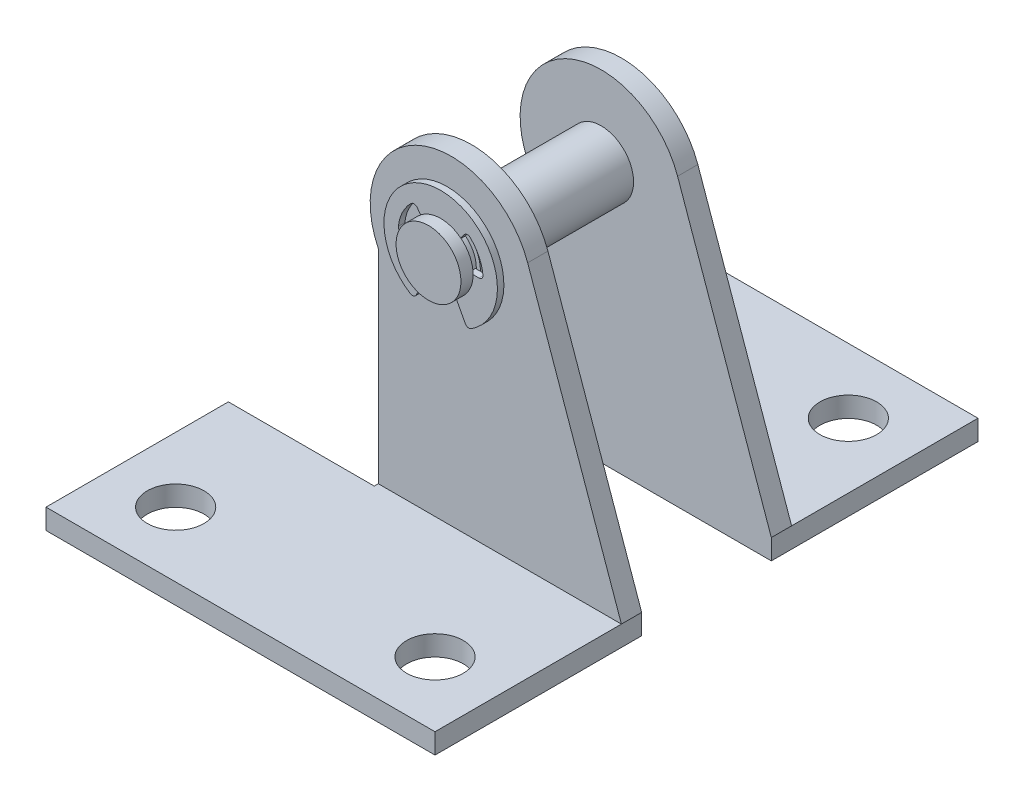
SolidWorks part; units mm, degrees
ref_plane "前视基准面" through (0, 0, 0) normal (0, 0, 1) x (1, 0, 0)
ref_plane "上视基准面" through (0, 0, 0) normal (0, 1, 0) x (1, 0, 0)
ref_plane "右视基准面" through (0, 0, 0) normal (1, 0, 0) x (0, 0, -1)
sketch "草图1" plane through (0, 0, 0) normal (1, 0, 0) x (0, 0, -1)
  line L0 (-13.3, 0) -> (-13.3, 4)
  line L1 (-13.3, 4) -> (-11.8, 4)
  line L2 (-11.8, 4) -> (-11.8, 3.5)
  line L3 (-11.8, 3.5) -> (-10.9, 3.5)
  line L4 (-10.9, 3.5) -> (-10.9, 4)
  line L5 (-10.9, 4) -> (10.9, 4)
  line L6 (10.9, 4) -> (10.9, 3.5)
  line L7 (10.9, 3.5) -> (11.8, 3.5)
  line L8 (11.8, 3.5) -> (11.8, 4)
  line L9 (11.8, 4) -> (13.3, 4)
  line L10 (13.3, 4) -> (13.3, 0)
  line L11 (13.3, 0) -> (-13.3, 0)
  line L12 (13.3, 0) -> (-13.3, 0) construction
revolve "旋转1" add sketch "草图1" angle 360 about L12 reverse direction yes
sketch "草图2" plane through (0, 0, 0) normal (0, 0, 1) x (1, 0, 0)
  line L0 (-9, -4.3589) -> (-9, -32)
  line L1 (-9, -32) -> (21, -32)
  line L2 (21, -32) -> (21, -29.5)
  line L3 (21, -29.5) -> (9.4314, 3.324)
  arc A0 (9.4314, 3.324) -> (-9, -4.3589) centre (0, 0) ccw
extrude "凸台-拉伸1" add sketch "草图2" against normal blind 10.5 and the other way blind 10.5
sketch "草图3" plane through (0, 0, 0) normal (1, 0, 0) x (0, 0, -1)
  line L0 (-8, 56) -> (-8, 4)
  line L1 (-8, 4) -> (8, 4)
  line L2 (8, 4) -> (8, 56)
  line L3 (8, 56) -> (-8, 56)
  line L4 (10, 0) -> (-10, 0) construction
revolve "切除-旋转1" cut sketch "草图3" angle 360 about L4 reverse direction yes
ref_plane "基准面4" through (0, -32, 0) normal (0, 1, 0) x (1, 0, 0)
sketch "草图4" plane through (0, -32, 0) normal (0, 1, 0) x (1, 0, 0)
  line L0 (-27, 33.5) -> (-27, -33.5)
  line L1 (-27, -33.5) -> (21, -33.5)
  line L2 (21, -33.5) -> (21, -8)
  line L3 (21, -8) -> (-9, -8)
  line L4 (-9, -8) -> (-9, 8)
  line L5 (-9, 8) -> (21, 8)
  line L6 (21, 8) -> (21, 33.5)
  line L7 (21, 33.5) -> (-27, 33.5)
  circle A0 centre (13, 25.5) radius 3.5
  circle A1 centre (13, -25.5) radius 3.5
  circle A2 centre (-19, 25.5) radius 3.5
  circle A3 centre (-19, -25.5) radius 3.5
extrude "凸台-拉伸2" add sketch "草图4" along normal blind 2.5
ref_plane "基准面5" through (-9, 0, 0) normal (1, 0, 0) x (0, 0, -1)
sketch "草图5" plane through (-9, 0, 0) normal (1, 0, 0) x (0, 0, -1)
  line L0 (-11, -29.5) -> (-11, -32)
  line L1 (-11, -32) -> (11, -32)
  line L2 (11, -32) -> (11, -29.5)
  line L3 (11, -29.5) -> (-11, -29.5)
extrude "切除-拉伸1" cut sketch "草图5" against normal blind 18
ref_plane "基准面6" through (0, 0, 11.8) normal (0, 0, 1) x (1, 0, 0)
sketch "草图6" plane through (0, 0, 11.8) normal (0, 0, 1) x (1, 0, 0)
  line L0 (-3.0425, -5.7222) -> (-1.6432, -3.0903)
  line L1 (-3.5, 0) -> (-4.7236, 0)
  line L2 (-2.9081, 3.7223) -> (-2.1548, 2.758)
  line L3 (2.1548, 2.758) -> (2.9081, 3.7223)
  line L4 (4.7236, 0) -> (3.5, 0)
  line L5 (1.6432, -3.0903) -> (3.0425, -5.7222)
  arc A0 (3.752, -5.9095) -> (-3.752, -5.9095) centre (0, 0) ccw
  arc A1 (-3.752, -5.9095) -> (-3.0425, -5.7222) centre (-3.484, -5.4874) ccw
  arc A2 (-1.6432, -3.0903) -> (-3.5, 0) centre (0, 0) cw
  arc A3 (-4.7236, 0) -> (-5.2208, 0.5526) centre (-4.7236, 0.5) cw
  arc A4 (-5.2208, 0.5526) -> (-3.6497, 3.7738) centre (0, 0) cw
  arc A5 (-3.6497, 3.7738) -> (-2.9081, 3.7223) centre (-3.3022, 3.4144) cw
  arc A6 (-2.1548, 2.758) -> (2.1548, 2.758) centre (0, 0) cw
  arc A7 (2.9081, 3.7223) -> (3.6497, 3.7738) centre (3.3022, 3.4144) cw
  arc A8 (3.6497, 3.7738) -> (5.2208, 0.5526) centre (0, 0) cw
  arc A9 (5.2208, 0.5526) -> (4.7236, 0) centre (4.7236, 0.5) cw
  arc A10 (3.5, 0) -> (1.6432, -3.0903) centre (0, 0) cw
  arc A11 (3.0425, -5.7222) -> (3.752, -5.9095) centre (3.484, -5.4874) ccw
extrude "凸台-拉伸3" add sketch "草图6" against normal blind 0.8
ref_plane "基准面7" through (0, 0, -11.8) normal (0, 0, 1) x (1, 0, 0)
sketch "草图7" plane through (0, 0, -11.8) normal (0, 0, 1) x (1, 0, 0)
  line L0 (-3.0425, -5.7222) -> (-1.6432, -3.0903)
  line L1 (-3.5, 0) -> (-4.7236, 0)
  line L2 (-2.9081, 3.7223) -> (-2.1548, 2.758)
  line L3 (2.1548, 2.758) -> (2.9081, 3.7223)
  line L4 (4.7236, 0) -> (3.5, 0)
  line L5 (1.6432, -3.0903) -> (3.0425, -5.7222)
  arc A0 (3.752, -5.9095) -> (-3.752, -5.9095) centre (0, 0) ccw
  arc A1 (-3.752, -5.9095) -> (-3.0425, -5.7222) centre (-3.484, -5.4874) ccw
  arc A2 (-1.6432, -3.0903) -> (-3.5, 0) centre (0, 0) cw
  arc A3 (-4.7236, 0) -> (-5.2208, 0.5526) centre (-4.7236, 0.5) cw
  arc A4 (-5.2208, 0.5526) -> (-3.6497, 3.7738) centre (0, 0) cw
  arc A5 (-3.6497, 3.7738) -> (-2.9081, 3.7223) centre (-3.3022, 3.4144) cw
  arc A6 (-2.1548, 2.758) -> (2.1548, 2.758) centre (0, 0) cw
  arc A7 (2.9081, 3.7223) -> (3.6497, 3.7738) centre (3.3022, 3.4144) cw
  arc A8 (3.6497, 3.7738) -> (5.2208, 0.5526) centre (0, 0) cw
  arc A9 (5.2208, 0.5526) -> (4.7236, 0) centre (4.7236, 0.5) cw
  arc A10 (3.5, 0) -> (1.6432, -3.0903) centre (0, 0) cw
  arc A11 (3.0425, -5.7222) -> (3.752, -5.9095) centre (3.484, -5.4874) ccw
extrude "凸台-拉伸4" add sketch "草图7" along normal blind 0.8
ref_plane "sdb XY" through (0, 0, 0) normal (0, 0, 1) x (1, 0, 0)
ref_plane "sdb XZ" through (0, 0, 0) normal (0, -1, 0) x (-1, 0, 0)
ref_plane "sdb YZ" through (0, 0, 0) normal (1, 0, 0) x (0, 0, -1)
ref_axis "sdb X" through (-80.9, 0, 0) along (1, 0, 0)
ref_axis "sdb Y" through (0, -50, 0) along (0, 1, 0)
ref_axis "sdb Z" through (0, 0, 80.9) along (0, 0, -1)
sketch3d "sdb"
  point P0 (0, 0, 0)
